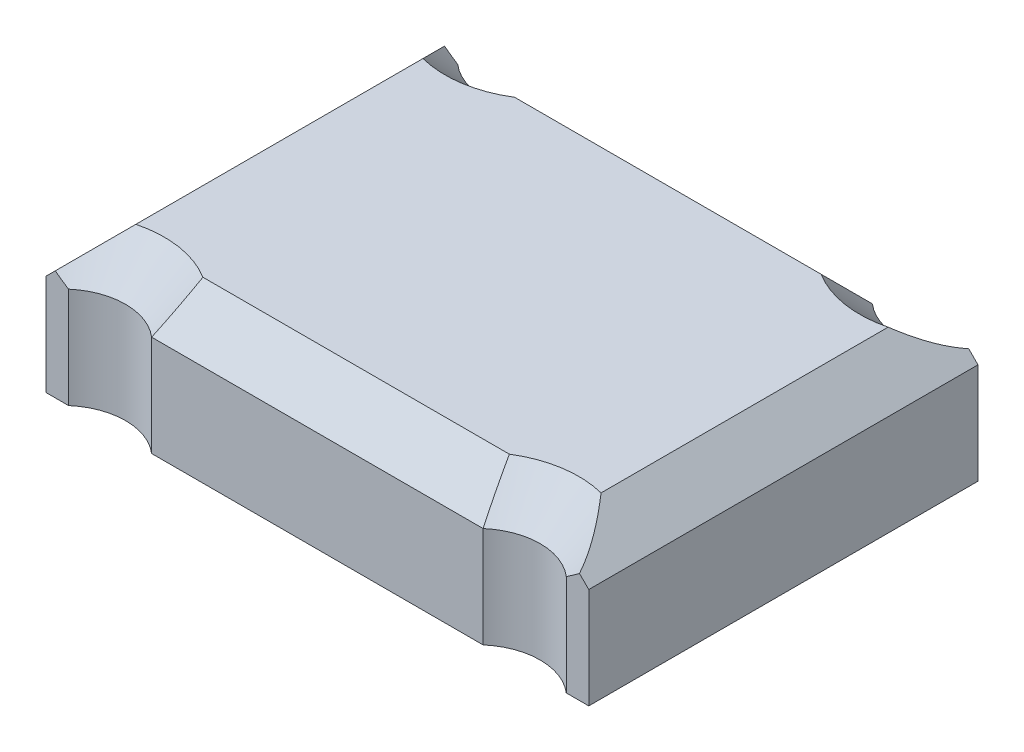
SolidWorks part; units mm, degrees
ref_plane "Спереди" through (0, 0, 0) normal (0, 0, 1) x (1, 0, 0)
ref_plane "Сверху" through (0, 0, 0) normal (0, 1, 0) x (1, 0, 0)
ref_plane "Справа" through (0, 0, 0) normal (1, 0, 0) x (0, 0, -1)
sketch "Эскиз1" plane through (0, 0, 0) normal (0, 1, 0) x (1, 0, 0)
  line L0 (-3.5, 2.51) -> (-3.2101, 2.51)
  line L1 (3.2101, 2.51) -> (3.5, 2.51)
  line L2 (-3.5, 2.51) -> (-3.5, -2.51)
  line L4 (3.5, 2.51) -> (3.5, -2.51)
  line L5 (-3.5, 2.51) -> (3.5, -2.51) construction
  line L6 (-3.5, -2.51) -> (3.5, 2.51) construction
  line L7 (-2.1374, 2.51) -> (2.1374, 2.51)
  line L8 (3.5, -2.51) -> (3.2101, -2.51)
  line L9 (2.1374, -2.51) -> (-2.1374, -2.51)
  line L10 (-3.2101, -2.51) -> (-3.5, -2.51)
  arc A0 (-3.2101, -2.51) -> (-2.1374, -2.51) centre (-2.6738, -3.1311) cw
  arc A1 (-3.2101, 2.51) -> (-2.1374, 2.51) centre (-2.6738, 3.1311) ccw
  arc A2 (3.2101, -2.51) -> (2.1374, -2.51) centre (2.6738, -3.1311) ccw
  arc A3 (3.2101, 2.51) -> (2.1374, 2.51) centre (2.6738, 3.1311) cw
  point P0 (0, 0)
extrude "Бобышка-Вытянуть1" add sketch "Эскиз1" along normal blind 1.8
chamfer "Фаска1" distance 0.5 angle 45 8 edges at (-3.5, 1.8, 0) (3.5, 1.8, 0) (2.6738, 1.8, 2.3105) (0, 1.8, 2.51) (-2.6738, 1.8, 2.3105) (-2.6738, 1.8, -2.3105) (0, 1.8, -2.51) (2.6738, 1.8, -2.3105)
